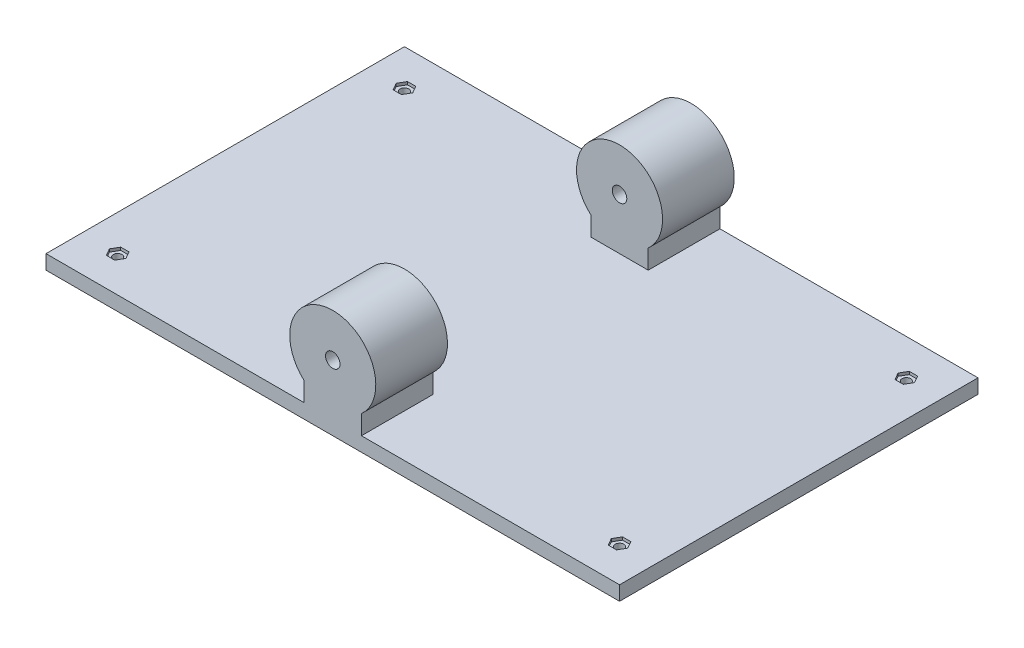
SolidWorks part; units mm, degrees
ref_plane "Front Plane" through (0, 0, 0) normal (0, 0, 1) x (1, 0, 0)
ref_plane "Top Plane" through (0, 0, 0) normal (0, 1, 0) x (1, 0, 0)
ref_plane "Right Plane" through (0, 0, 0) normal (1, 0, 0) x (0, 0, -1)
sketch "Sketch1" plane through (0, 0, 0) normal (0, 1, 0) x (1, 0, 0)
  line L0 (200, 250) -> (200, 0) construction
  line L1 (0, 0) -> (400, 0)
  line L2 (0, 0) -> (0, 250)
  line L3 (0, 250) -> (400, 250)
  line L4 (400, 0) -> (400, 250)
  line L5 (25, 225) -> (375, 225) construction
  line L6 (375, 25) -> (375, 225) construction
  line L7 (25, 25) -> (375, 25) construction
  line L8 (25, 25) -> (25, 225) construction
  line L9 (200, 125) -> (25, 125) construction
  line L10 (30.7735, 225) -> (27.8868, 230) construction
  line L11 (27.8868, 230) -> (22.1132, 230) construction
  line L12 (22.1132, 230) -> (19.2265, 225) construction
  line L13 (19.2265, 225) -> (22.1132, 220) construction
  line L14 (22.1132, 220) -> (27.8868, 220) construction
  line L15 (27.8868, 220) -> (30.7735, 225) construction
  line L16 (27.8868, 30) -> (30.7735, 25) construction
  line L17 (22.1132, 30) -> (27.8868, 30) construction
  line L18 (19.2265, 25) -> (22.1132, 30) construction
  line L19 (22.1132, 20) -> (19.2265, 25) construction
  line L20 (27.8868, 20) -> (22.1132, 20) construction
  line L21 (30.7735, 25) -> (27.8868, 20) construction
  line L22 (377.8868, 30) -> (372.1132, 30) construction
  line L23 (380.7735, 25) -> (377.8868, 30) construction
  line L24 (377.8868, 20) -> (380.7735, 25) construction
  line L25 (372.1132, 20) -> (377.8868, 20) construction
  line L26 (369.2265, 25) -> (372.1132, 20) construction
  line L27 (372.1132, 30) -> (369.2265, 25) construction
  line L28 (372.1132, 220) -> (369.2265, 225) construction
  line L29 (377.8868, 220) -> (372.1132, 220) construction
  line L30 (380.7735, 225) -> (377.8868, 220) construction
  line L31 (377.8868, 230) -> (380.7735, 225) construction
  line L32 (372.1132, 230) -> (377.8868, 230) construction
  line L33 (369.2265, 225) -> (372.1132, 230) construction
  circle A0 centre (25, 225) radius 3
  circle A1 centre (25, 225) radius 5 construction
  circle A2 centre (25, 25) radius 3
  circle A3 centre (375, 25) radius 3
  circle A4 centre (375, 225) radius 3
  dimension "D3" = 6
  dimension "D1" = 400
  dimension "D2" = 250
  dimension "D5" = 10
  dimension "D4" = 25
extrude "Boss-Extrude1" add sketch "Sketch1" along normal blind 10
sketch "Sketch6" plane through (0, 10, 0) normal (0, 1, 0) x (1, 0, 0)
  line L0 (200, 250) -> (200, 0) construction
  line L1 (30.7735, 225) -> (27.8868, 230)
  line L2 (27.8868, 230) -> (22.1132, 230)
  line L3 (22.1132, 230) -> (19.2265, 225)
  line L4 (19.2265, 225) -> (22.1132, 220)
  line L5 (22.1132, 220) -> (27.8868, 220)
  line L6 (27.8868, 220) -> (30.7735, 225)
  line L7 (400, 250) -> (0, 250) construction
  line L8 (0, 0) -> (400, 0) construction
  line L9 (200, 125) -> (0, 125) construction
  line L10 (0, 250) -> (0, 0) construction
  line L11 (27.8868, 30) -> (30.7735, 25)
  line L12 (22.1132, 30) -> (27.8868, 30)
  line L13 (19.2265, 25) -> (22.1132, 30)
  line L14 (22.1132, 20) -> (19.2265, 25)
  line L15 (27.8868, 20) -> (22.1132, 20)
  line L16 (30.7735, 25) -> (27.8868, 20)
  line L17 (377.8868, 30) -> (372.1132, 30)
  line L18 (380.7735, 25) -> (377.8868, 30)
  line L19 (377.8868, 20) -> (380.7735, 25)
  line L20 (372.1132, 20) -> (377.8868, 20)
  line L21 (369.2265, 25) -> (372.1132, 20)
  line L22 (372.1132, 30) -> (369.2265, 25)
  line L23 (372.1132, 220) -> (369.2265, 225)
  line L24 (377.8868, 220) -> (372.1132, 220)
  line L25 (380.7735, 225) -> (377.8868, 220)
  line L26 (377.8868, 230) -> (380.7735, 225)
  line L27 (372.1132, 230) -> (377.8868, 230)
  line L28 (369.2265, 225) -> (372.1132, 230)
  circle A0 centre (25, 225) radius 5 construction
  dimension "D1" = 10
extrude "Cut-Extrude1" cut sketch "Sketch6" against normal blind 2
sketch "Sketch7" plane through (0, 10, 0) normal (0, 1, 0) x (1, 0, 0)
  line L0 (0, 0) -> (400, 0) construction
  line L1 (180, 0) -> (220, 0)
  line L2 (180, 0) -> (180, 50)
  line L3 (180, 50) -> (220, 50)
  line L4 (220, 0) -> (220, 50)
  point P6 (200, 0)
  point P7 (200, 0)
  dimension "D1" = 40
  dimension "D2" = 50
extrude "Boss-Extrude2" add sketch "Sketch7" along normal blind 13.3772
sketch "Sketch8" plane through (0, 0, 0) normal (0, 0, 1) x (1, 0, 0)
  circle A0 centre (200, 45.7379) radius 30
  circle A1 centre (200, 45.7379) radius 5.05
  dimension "D1" = 60
  dimension "D2" = 10.1
extrude "Boss-Extrude3" add sketch "Sketch8" against normal up to surface (50 mm away) up to face at (200, 16.6886, -50)
ref_plane "Plane1" through (0, 0, -125) normal (0, 0, 1) x (1, 0, 0)
mirror "Mirror2" about plane through (0, 0, -125) normal (0, 0, 1) of "Boss-Extrude2", "Boss-Extrude3"
equation "\"joint_width\"=4"
equation "\"D2@Sketch7\"=\"short_base_length\"/5"
equation "\"short_base_length\"=25"
equation "\"D2@Sketch1\"=\"short_base_length\""
equation "\"outer_rad_main_joint\"=6"
equation "\"outer_diam_main_joint\"=6"
equation "\"D1@Sketch8\"=\"outer_diam_main_joint\""
equation "\"D1@Sketch7\"=\"outer_rad_main_joint\"-2"
equation "\"D1@Boss-Extrude2\"=\"outer_diam_main_joint\"/2+(1.50cm) - sqr(((\"outer_diam_main_joint\"/2)^2)+((\"outer_diam_main_joint\"/2-2)^2))"
